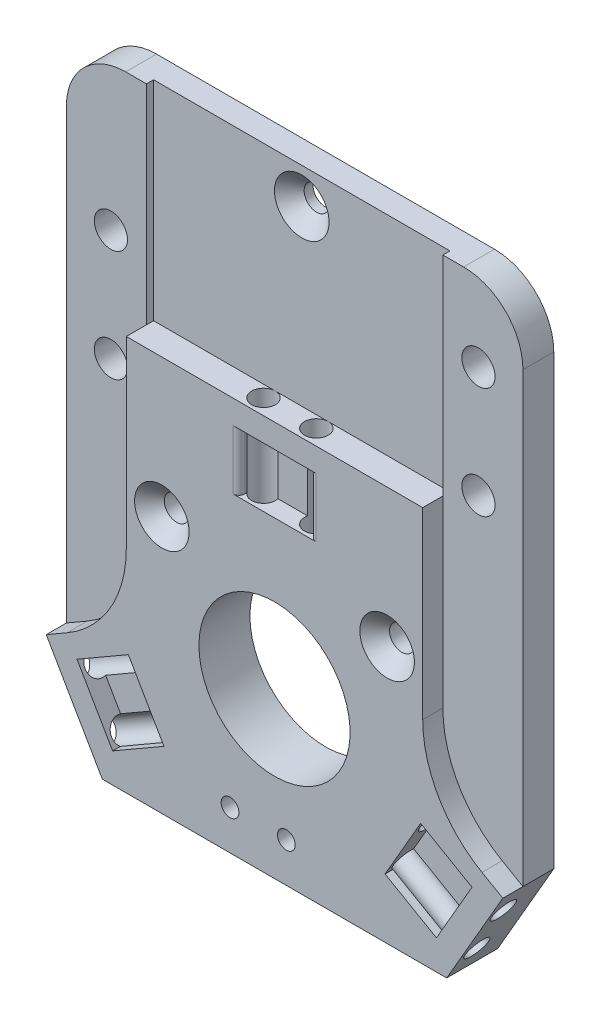
SolidWorks part; units mm, degrees
other "carriage coupler plate"
material "PET"
ref_plane "Front" through (0, 0, 0) normal (0, 0, 1) x (1, 0, 0)
ref_plane "Top" through (0, 0, 0) normal (0, 1, 0) x (1, 0, 0)
ref_plane "Right" through (0, 0, 0) normal (1, 0, 0) x (0, 0, -1)
sketch "Sketch1" plane through (0, 0, 0) normal (0, 0, 1) x (1, 0, 0)
  line L0 (0, 0) -> (0, 30) construction
  line L1 (0, 0) -> (25.9808, -15) construction
  line L2 (0, 0) -> (-25.9808, -15) construction
  dimension "D1" = 120
  dimension "D2" = 120
  dimension "D3" = 30
ref_plane "Plane1" through (0, 30, 0) normal (0, 1, 0) x (1, 0, 0)
sketch "Sketch2" plane through (0, 30, 0) normal (0, 1, 0) x (1, 0, 0)
  line L0 (-4.4589, 0) -> (0, -4.0148) construction
  line L1 (0, 0) -> (-25.9808, 0) construction
  line L2 (0, 0) -> (0, -4.0148) construction
  line L3 (-4.4589, 0) -> (0, 0) construction
  line L4 (0, -5.3962) -> (0, -4.0148) construction
  line L5 (0, -5.3962) -> (-4.4589, 0) construction
  line L7 (-4, -4.0148) -> (4, -4.0148) construction
  line L8 (3.9519, -3.3962) -> (-3.9519, -3.3962) construction
  line L9 (0, -0.3962) -> (0, -3.3962) construction
  line L10 (0, -4.0148) -> (0, -7.3926) construction
  circle A0 centre (-4.4589, 0) radius 2
  circle A1 centre (4.4589, 0) radius 2
  circle A2 centre (0, -4.0148) radius 4
  circle A3 centre (0, -5.3962) radius 5 construction
  circle A4 centre (0, -7.3926) radius 1.5
  dimension "D1" = 4
  dimension "D2" = 8
  dimension "D4" = 10
  dimension "D9" = 3
  dimension "D6" = 7.3926
  dimension "D8" = 8.9177
  dimension "D3" = 42
  dimension "D5" = 50.433
  dimension "D7" = 3.3962
  dimension "D10" = 0.6186
sketch "Sketch3" plane through (0, 0, 0) normal (0, 0, 1) x (1, 0, 0)
  line L0 (0, 30) -> (0, 35) construction
  line L2 (0, 35) -> (0, 39) construction
  line L3 (-25, 39) -> (25, 39)
  line L4 (25, 39) -> (25, -3.5116)
  line L5 (25, -3.5116) -> (38.5044, -11.3084)
  line L6 (0, 0) -> (0, 30) construction
  line L7 (-25, -3.5116) -> (-38.5044, -11.3084)
  line L8 (-25, 39) -> (-25, -3.5116)
  line L9 (4.4589, 30) -> (4.4589, 39) construction
  line L10 (25.9808, -15) -> (33.775, -19.5) construction
  line L11 (29.0456, -27.6916) -> (-29.0456, -27.6916)
  line L13 (0, 0) -> (25.9808, -15) construction
  line L14 (33.775, -19.5) -> (38.5044, -11.3084)
  line L15 (4.4589, 30) -> (0, 30) construction
  line L16 (4.4589, 30) -> (9.4589, 30) construction
  line L17 (-33.775, -19.5) -> (-38.5044, -11.3084)
  line L18 (33.775, -19.5) -> (29.0456, -27.6916)
  line L19 (-33.775, -19.5) -> (-29.0456, -27.6916)
  dimension "D1" = 5
  dimension "D2" = 4
  dimension "D3" = 25
  dimension "D4" = 120
  dimension "D5" = 5
  dimension "D6" = 9.4589
  dimension "D7" = 9.4589
  dimension "D8" = 9
  dimension "D9" = 9
extrude "Boss-Extrude1" add sketch "Sketch3" along normal blind 2.6 and the other way blind 6
fillet "Fillet1" radius 20 2 edges at (-25, -3.5116, -1.7) (25, -3.5116, -1.7)
sketch "Sketch4" plane through (0, 30, 0) normal (0, 1, 0) x (1, 0, 0)
  line L0 (0, -0.0148) -> (0, 0.4852) construction
  line L1 (5.1148, 0.4852) -> (-5.1148, 0.4852)
  line L2 (-5.1148, 0.4852) -> (-6, -0.4)
  line L3 (-6, -0.4) -> (-6, -2.6)
  line L4 (25, -2.6) -> (-25, -2.6) construction
  line L5 (-6, -2.6) -> (6, -2.6)
  line L7 (0, -5.3962) -> (-4.4589, 0) construction
  line L8 (-0.7342, -4.5076) -> (-0.5833, -4.3426)
  line L9 (6, -0.4) -> (6, -2.6)
  line L10 (5.1148, 0.4852) -> (6, -0.4)
  circle A7 centre (0, -4.0148) radius 4 construction
  dimension "D1" = 0.5
  dimension "D2" = 135
  dimension "D3" = 12
  dimension "D4" = 2.2
extrude "Cut-Extrude1" cut sketch "Sketch4" against normal blind 5 and the other way blind 5 contours L5 L9 L10 L1 L2 L3
sketch "Sketch5" plane through (0, 39, 0) normal (0, 1, 0) x (1, 0, 0)
  circle A0 centre (-4.4589, 0) radius 2 construction
  circle A1 centre (4.4589, 0) radius 2 construction
  circle A2 centre (-4.4589, 0) radius 2
  circle A3 centre (4.4589, 0) radius 2
extrude "Cut-Extrude2" cut sketch "Sketch5" against normal blind 20
fillet "Fillet3" radius 1 2 edges at (-6, 30, 2.6) (6, 30, 2.6)
ref_axis "Axis1" through (0, 0, -80.9) along (0, 0, 1)
pattern_circular "CirPattern1" count 3 over 360 about axis through (0, 0, -80.9) along (0, 0, 1) of "Cut-Extrude2", "Cut-Extrude1"
sketch "Sketch6" plane through (0, 0, 2.6) normal (0, 0, 1) x (1, 0, 0)
  circle A0 centre (0, 0) radius 2.75
  dimension "D1" = 5.5
extrude "Cut-Extrude3" cut sketch "Sketch6" against normal through all
sketch "Sketch7" plane through (0, 0, -6) normal (0, 0, -1) x (-1, 0, 0)
  line L2 (0, 0) -> (0, 68.2) construction
  line L3 (-25, 39) -> (25, 39) construction
  line L4 (-25, 39) -> (25, 39)
  line L5 (-25, 39) -> (-25, 54)
  line L6 (-25, 54) -> (-3.9868, 72.6839)
  line L7 (25, 39) -> (25, 54)
  line L8 (25, 54) -> (3.9868, 72.6839)
  arc A0 (3.9868, 72.6839) -> (-3.9868, 72.6839) centre (0, 68.2) ccw
  dimension "D1" = 12
  dimension "D2" = 29.2
  dimension "D3" = 15
extrude "Boss-Extrude2" add sketch "Sketch7" against normal blind 4
sketch "Sketch8" plane through (0, 0, 2.6) normal (0, 0, 1) x (1, 0, 0)
  line L0 (0, 0) -> (0, 68.2) construction
  line L1 (-19, 15.7) -> (19, 15.7) construction
  circle A0 centre (-19, 15.7) radius 2.1
  circle A1 centre (19, 15.7) radius 2.1
  circle A2 centre (0, 68.2) radius 2.1
  arc A3 (3.9868, 72.6839) -> (-3.9868, 72.6839) centre (0, 68.2) ccw construction
  point P10 (0, 15.7)
  dimension "D1" = 4.2
  dimension "D2" = 4.2
  dimension "D3" = 4.2
  dimension "D4" = 52.5
  dimension "D5" = 38
extrude "Cut-Extrude4" cut sketch "Sketch8" against normal through all
chamfer "Chamfer1" distance 2.5 angle 45 3 edges at (-16.9, 15.7, 2.6) (21.1, 15.7, 2.6) (-2.1, 68.2, -2)
sketch "Sketch9" plane through (0, 0, -6) normal (0, 0, -1) x (-1, 0, 0)
  line L0 (0, -27.6916) -> (0, -6.1064) construction
  line L1 (29.0456, -27.6916) -> (-29.0456, -27.6916) construction
  line L2 (-2, -21.0416) -> (7.5, -21.0416) construction
  circle A0 centre (7.5, -21.0416) radius 1.5
  circle A1 centre (-2, -21.0416) radius 1.5
  dimension "D4" = 3
  dimension "D5" = 3
  dimension "D1" = 6.65
  dimension "D2" = 7.5
  dimension "D3" = 9.5
extrude "Cut-Extrude5" cut sketch "Sketch9" against normal through all
sketch "Sketch10" plane through (0, 0, -6) normal (0, 0, -1) x (-1, 0, 0)
  line L2 (25, 8.0354) -> (25, 54)
  line L4 (38.5044, -11.3084) -> (38.5044, 74.2)
  line L8 (35, -9.2851) -> (38.5044, -11.3084)
  line L10 (0, 74.2) -> (38.5044, 74.2)
  line L11 (25, 54) -> (3.9868, 72.6839)
  arc A0 (3.9868, 72.6839) -> (-3.9868, 72.6839) centre (0, 68.2) ccw construction
  arc A2 (35, -9.2851) -> (25, 8.0354) centre (45, 8.0354) cw
  arc A3 (0, 74.2) -> (3.9868, 72.6839) centre (0, 68.2) cw
extrude "Boss-Extrude3" add sketch "Sketch10" against normal blind 5.2
sketch "Sketch11" plane through (0, 0, -6) normal (0, 0, -1) x (-1, 0, 0)
  line L0 (-38.5044, -11.3084) -> (-38.5044, 74.2)
  line L2 (-38.5044, -11.3084) -> (-35, -9.2851)
  line L3 (-25, 8.0354) -> (-25, 54)
  line L12 (-38.5044, 74.2) -> (0.121, 74.2)
  line L14 (0.121, 74.2) -> (-25, 54)
  line L15 (38.5044, 74.2) -> (0, 74.2) construction
  arc A2 (-35, -9.2851) -> (-25, 8.0354) centre (-45, 8.0354) ccw
  circle A6 centre (0, 68.2) radius 4.6 construction
extrude "Boss-Extrude4" add sketch "Sketch11" against normal blind 5.2
sketch "Sketch12" plane through (0, 0, -0.8) normal (0, 0, 1) x (1, 0, 0)
  line L0 (-38.5044, 49.8275) -> (-31, 49.8275) construction
  line L1 (-38.5044, -11.3084) -> (-38.5044, 74.2) construction
  line L2 (38.5044, 60.8275) -> (31, 60.8275) construction
  line L3 (38.5044, 74.2) -> (38.5044, -11.3084) construction
  line L4 (25, 8.0354) -> (25, 39) construction
  line L5 (-25, 39) -> (-25, 8.0354) construction
  line L6 (25, 39) -> (-25, 39) construction
  line L7 (-31, 49.8275) -> (-31, 31.0775) construction
  line L8 (25, 39) -> (4.4589, 39) construction
  line L9 (31, 60.8275) -> (31, 42.0775) construction
  circle A0 centre (-31, 49.8275) radius 2.8
  circle A1 centre (31, 60.8275) radius 2.8
  circle A2 centre (-31, 31.0775) radius 2.8
  circle A3 centre (31, 42.0775) radius 2.8
  dimension "D5" = 5.6
  dimension "D6" = 5.6
  dimension "D7" = 5.6
  dimension "D9" = 5.6
  dimension "D1" = 10.8275
  dimension "D2" = 21.8275
  dimension "D3" = 6
  dimension "D4" = 6
  dimension "D8" = 18.75
  dimension "D10" = 18.75
fillet "Fillet4" radius 10 2 edges at (-38.5044, 74.2, -3.4) (38.5044, 74.2, -3.4)
sketch "Sketch13" plane through (0, 0, -6) normal (0, 0, -1) x (-1, 0, 0)
  circle A0 centre (0, 0) radius 7
  dimension "D1" = 14
extrude "Cut-Extrude7" cut sketch "Sketch13" against normal blind 5
sketch "Sketch14" plane through (0, 0, -0.8) normal (0, 0, 1) x (1, 0, 0)
  line L1 (-25, 39) -> (25, 39)
  line L2 (-25, 39) -> (-25, 74.2)
  line L3 (-25, 74.2) -> (25, 74.2)
  line L4 (25, 39) -> (25, 74.2)
  line L5 (25, 8.0354) -> (25, 39) construction
  line L6 (-28.5044, 74.2) -> (28.5044, 74.2) construction
extrude "Cut-Extrude8" cut sketch "Sketch14" against normal up to surface (1.2 mm away) up to face at (-0.5959, 55.1213, -2)
hole_wizard "Ø5.6 (5.6) Diameter Hole1" positions "Sketch15" profile "Sketch16" hole size "Ø5.6" standard "ANSI Metric" end condition through all
sketch "Sketch15" plane through (0, 0, -0.8) normal (0, 0, 1) x (1, 0, 0)
  point P0 (-31, 49.8275)
  point P3 (-31, 31.0775)
  point P6 (31, 42.0775)
  point P9 (31, 60.8275)
sketch "Sketch16" plane through (-31, 49.8275, -0.8) normal (1, 0, 0) x (0, -1, 0)
  line L0 (0, 0) -> (0, 5.2)
  line L1 (0, 5.2) -> (2.8, 5.2)
  line L2 (2.8, 5.2) -> (2.8, 0)
  line L5 (2.8, 0) -> (0, 0)
  line L11 (0, -6.35) -> (0, 107.95) construction
  dimension "Thru Hole Dia." = 5.6
  dimension "Thru Hole Depth" = 5.2
sketch "Sketch17" plane through (0, 0, -6) normal (0, 0, -1) x (-1, 0, 0)
  circle A0 centre (0, 0) radius 12.75
  dimension "D1" = 25.5
extrude "Cut-Extrude9" cut sketch "Sketch17" against normal through all
